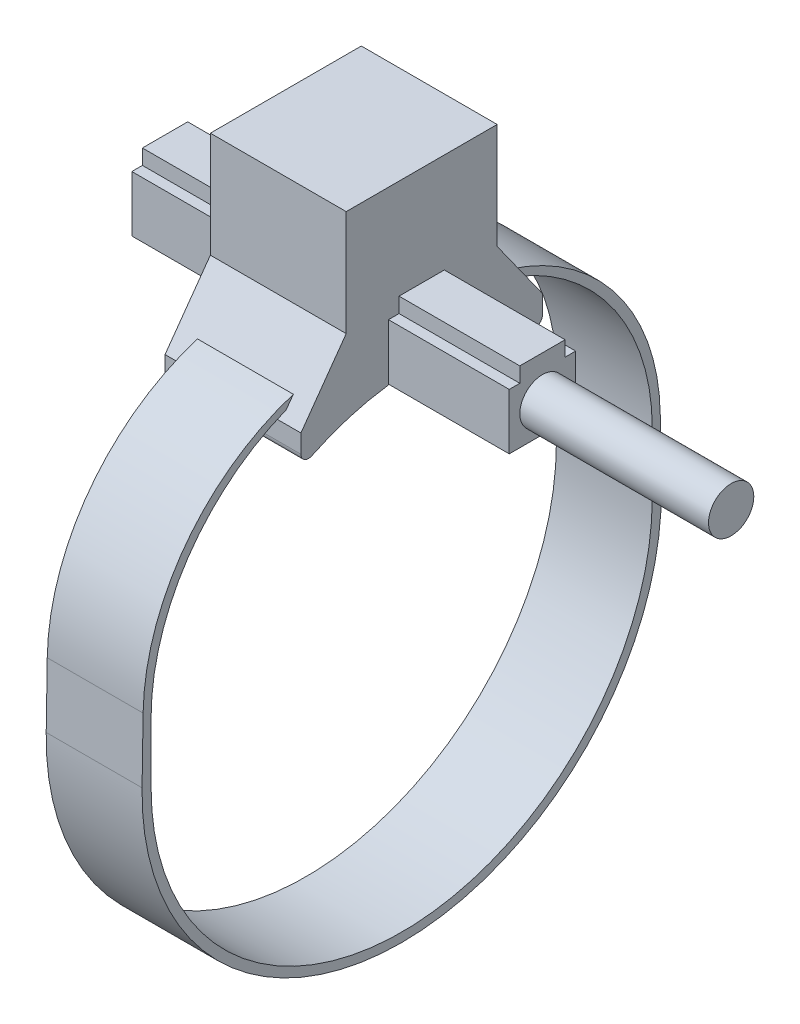
SolidWorks part; units mm, degrees
ref_plane "前视基准面" through (0, 0, 0) normal (0, 0, 1) x (1, 0, 0)
ref_plane "上视基准面" through (0, 0, 0) normal (0, 1, 0) x (1, 0, 0)
ref_plane "右视基准面" through (0, 0, 0) normal (1, 0, 0) x (0, 0, -1)
ref_plane "基准面4" through (11.5, 0, 0) normal (1, 0, 0) x (0, 0, -1)
sketch "草图1" plane through (11.5, 0, 0) normal (1, 0, 0) x (0, 0, -1)
  line L0 (-8, 16.7) -> (-8, 15.4787)
  line L1 (-2.2, 16.5545) -> (-2.2, 19.9)
  line L2 (-2.2, 19.9) -> (-1.5, 19.9)
  line L3 (-1.5, 19.9) -> (-1.5, 20.9)
  line L4 (-1.5, 20.9) -> (1.5, 20.9)
  line L5 (1.5, 20.9) -> (1.5, 19.9)
  line L6 (1.5, 19.9) -> (2.2, 19.9)
  line L7 (2.2, 19.9) -> (2.2, 16.5545)
  line L8 (8, 15.4787) -> (8, 16.7)
  line L9 (8, 16.7) -> (5, 20.9)
  line L10 (5, 20.9) -> (5, 27.9)
  line L11 (5, 27.9) -> (-5, 27.9)
  line L12 (-5, 27.9) -> (-5, 20.9)
  line L13 (-5, 20.9) -> (-8, 16.7)
  arc A0 (-8, 15.4787) -> (-7.282, 15.0287) centre (-7.5, 15.4787) ccw
  arc A1 (-7.282, 15.0287) -> (-2.2, 16.5545) centre (0, 0) cw
  arc A2 (2.2, 16.5545) -> (7.282, 15.0287) centre (0, 0) cw
  arc A3 (7.282, 15.0287) -> (8, 15.4787) centre (7.5, 15.4787) ccw
extrude "凸台-拉伸1" add sketch "草图1" against normal blind 4.5 and the other way blind 4.5
sketch "草图2" plane through (11.5, 0, 0) normal (1, 0, 0) x (0, 0, -1)
  line L0 (17.1977, 0.281) -> (17.1282, 4.532)
  line L1 (2.9301, 18.5) -> (-2.9301, 18.5)
  line L2 (-17.1282, 4.532) -> (-17.1977, 0.281)
  line L3 (16.6, 0) -> (16.6, 4)
  line L4 (2.4, 18.2) -> (-2.4, 18.2)
  line L5 (-16.6, 4) -> (-16.6, 0)
  arc A0 (-17.1977, 0.281) -> (17.1977, 0.281) centre (0, 0) ccw
  arc A1 (17.1282, 4.532) -> (2.9301, 18.5) centre (2.9301, 4.3) ccw
  arc A2 (-2.9301, 18.5) -> (-17.1282, 4.532) centre (-2.9301, 4.3) ccw
  arc A3 (-16.6, 0) -> (16.6, 0) centre (0, 0) ccw
  arc A4 (16.6, 4) -> (2.4, 18.2) centre (2.4, 4) ccw
  arc A5 (-2.4, 18.2) -> (-16.6, 4) centre (-2.4, 4) ccw
extrude "凸台-拉伸2" add sketch "草图2" against normal blind 3.175 and the other way blind 3.175
sketch "草图3" plane through (11.5, 0, 0) normal (1, 0, 0) x (0, 0, -1)
  line L0 (-2.2, 20.3) -> (-2.2, 16.6)
  line L1 (-2.2, 16.6) -> (2.2, 16.6)
  line L2 (2.2, 16.6) -> (2.2, 20.3)
  line L3 (2.2, 20.3) -> (1.5, 20.3)
  line L4 (1.5, 20.3) -> (1.5, 21.3)
  line L5 (1.5, 21.3) -> (-1.5, 21.3)
  line L6 (-1.5, 21.3) -> (-1.5, 20.3)
  line L7 (-1.5, 20.3) -> (-2.2, 20.3)
extrude "凸台-拉伸3" add sketch "草图3" against normal blind 12.5 and the other way blind 12.5
sketch "草图4" plane through (11.5, 0, 0) normal (1, 0, 0) x (0, 0, -1)
  circle A0 centre (0, 18.55) radius 1.5
extrude "凸台-拉伸4" add sketch "草图4" along normal blind 25
ref_plane "基准面5" through (7.1, 0, 0) normal (1, 0, 0) x (0, 0, -1)
ref_plane "CS1_M XY" through (0, 0, 0) normal (1, 0, 0) x (0, 0, -1)
ref_plane "CS1_M XZ" through (0, 0, 0) normal (0, -1, 0) x (-1, 0, 0)
ref_plane "CS1_M YZ" through (0, 0, 0) normal (0, 0, -1) x (-1, 0, 0)
ref_axis "CS1_M X" through (0, 0, 80.9) along (0, 0, -1)
ref_axis "CS1_M Y" through (0, -50, 0) along (0, 1, 0)
ref_axis "CS1_M Z" through (80.9, 0, 0) along (-1, 0, 0)
sketch3d "CS1_M"
  point P0 (0, 0, 0)
